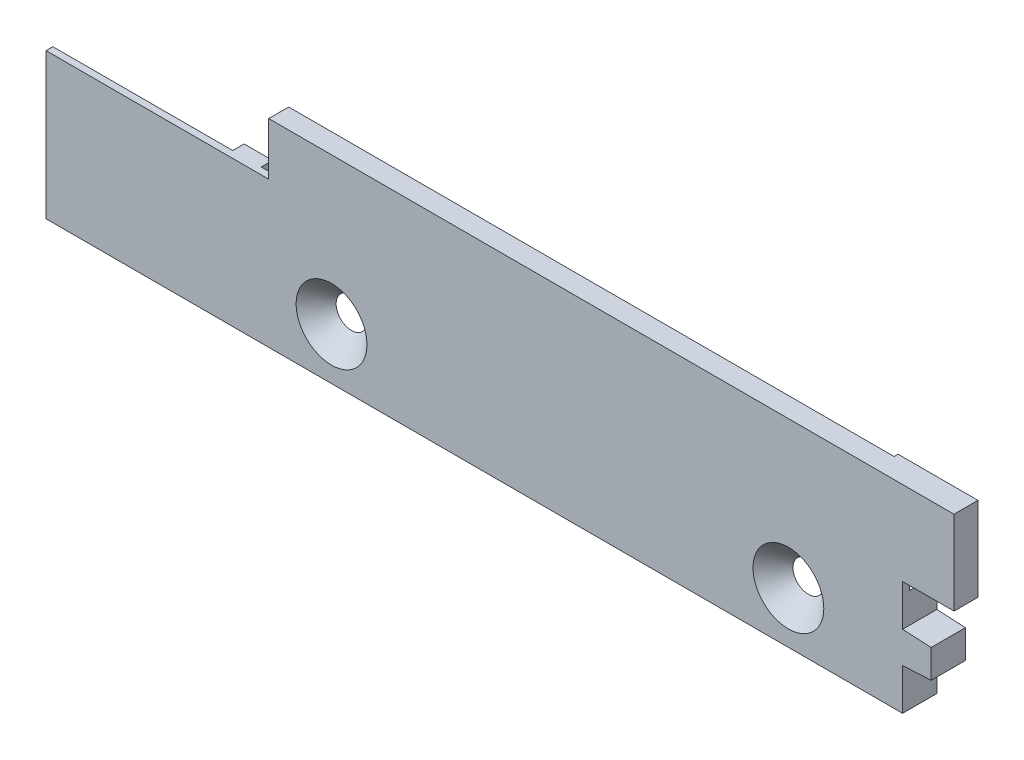
SolidWorks part; units mm, degrees
ref_plane "Front Plane" through (0, 0, 0) normal (0, 0, 1) x (1, 0, 0)
ref_plane "Top Plane" through (0, 0, 0) normal (0, 1, 0) x (1, 0, 0)
ref_plane "Right Plane" through (0, 0, 0) normal (1, 0, 0) x (0, 0, -1)
ref_axis "X-Axis" through (0, 0, 0) along (1, 0, 0)
ref_axis "Y-Axis" through (0, 42.2917, 0) along (0, -1, 0)
ref_axis "Z-Axis" through (0, 0, 55.0015) along (0, 0, -1)
sketch "Sketch1" plane through (0, 0, 0) normal (0, 0, 1) x (1, 0, 0)
  line L1 (-127.8191, -9.8629) -> (22.1809, -9.8629)
  line L2 (22.1809, -9.8629) -> (22.1809, -2.6129)
  line L3 (22.1809, -2.6129) -> (27.1809, -2.6129)
  line L4 (27.1809, -2.6129) -> (27.1809, 2.8871)
  line L5 (27.1809, 2.8871) -> (22.1809, 2.8871)
  line L6 (22.1809, 2.8871) -> (22.1809, 10.1371)
  line L7 (22.1809, 10.1371) -> (31.1809, 10.1371)
  line L8 (31.1809, 10.1371) -> (31.1809, 23.6371)
  line L10 (-127.8191, 15.6371) -> (-127.8191, -9.8629)
  line L12 (-88.8191, -25.8695) -> (-88.8191, 48.9262) construction
  line L13 (31.1809, 13.1371) -> (10.3885, 13.1371) construction
  line L14 (31.1809, 23.6371) -> (-88.8191, 23.6371) construction
  line L15 (-88.8191, 23.6371) -> (-88.8191, 15.6371)
  line L16 (-88.8191, 15.6371) -> (-127.8191, 15.6371)
  line L17 (31.1809, 23.6371) -> (31.1809, 24.8371)
  line L18 (31.1809, 24.8371) -> (-88.8191, 24.8371)
  line L19 (-88.8191, 24.8371) -> (-88.8191, 23.6371)
  point P5 (27.1809, 0.1371)
  dimension "D2" = 10
  dimension "D3" = 20
  dimension "D4" = 5.5
  dimension "D5" = 9
  dimension "D6" = 150
  dimension "D7" = 120
  dimension "D8" = 5
  dimension "D10" = 3
  dimension "D11" = 8
  dimension "D12" = 10.5
  dimension "D13" = 1.2
extrude "Boss-Extrude1" add sketch "Sketch1" along normal blind 6 and the other way blind 6
sketch "Sketch2" plane through (-127.8191, 0, 0) normal (-1, 0, 0) x (0, 0, 1)
  line L0 (-6, -9.8629) -> (6, -9.8629) construction
  line L1 (-4.8, 23.1371) -> (4.8, 23.1371) construction
  line L2 (-4.8, 23.1371) -> (-4.8, 8.1371)
  line L3 (-4.8, 8.1371) -> (4.8, 8.1371)
  line L4 (4.8, 23.1371) -> (4.8, 8.1371)
  line L5 (-6, 24.8371) -> (-6, 15.6371) construction
  line L7 (-6, 2.8871) -> (6, 2.8871) construction
  line L8 (-6, 15.6371) -> (-6, -9.8629) construction
  line L9 (6, 15.6371) -> (6, -9.8629) construction
  line L10 (0, 2.8871) -> (0, 23.1371) construction
  line L11 (-4.8, 23.1371) -> (-1.8, 23.1371)
  line L12 (-1.8, 23.1371) -> (-1.8, 24.8371)
  line L13 (-6, 24.8371) -> (6, 24.8371) construction
  line L14 (-1.8, 24.8371) -> (1.8, 24.8371)
  line L15 (1.8, 24.8371) -> (1.8, 23.1371)
  line L16 (1.8, 23.1371) -> (4.8, 23.1371)
  point P6 (0, 23.1371)
  dimension "D1" = 9.6
  dimension "D2" = 33
  dimension "D3" = 3
  dimension "D4" = 3
  dimension "D6" = 18
  dimension "D7" = 1.2
extrude "Cut-Extrude1" cut sketch "Sketch2" against normal offset from surface (157 mm away) 2 up to face at (31.1809, 17.4871, 0)
sketch "Sketch8" plane through (0, 0, 0) normal (0, 0, 1) x (1, 0, 0)
  line L0 (-127.8191, 15.6371) -> (-127.8191, -9.8629) construction
  line L1 (-107.8191, 24.8371) -> (17.1809, 24.8371)
  line L2 (-107.8191, 24.8371) -> (-107.8191, -9.8629)
  line L3 (-107.8191, -9.8629) -> (17.1809, -9.8629)
  line L4 (17.1809, 24.8371) -> (17.1809, -9.8629)
  line L5 (-127.8191, -9.8629) -> (22.1809, -9.8629) construction
  line L7 (22.1809, 2.8871) -> (22.1809, 10.1371) construction
  line L8 (29.1809, 24.8371) -> (-88.8191, 24.8371) construction
  point P12 (22.1809, 6.5121)
  dimension "D1" = 20
  dimension "D2" = 5
extrude "Cut-Extrude4" cut sketch "Sketch8" against normal blind 2.5 and the other way blind 2.5 contours L2 L3 L4 L1
sketch "Sketch9" plane through (0, 0, 0) normal (0, 0, 1) x (1, 0, 0)
  line L0 (-107.8191, -0.8629) -> (17.1809, -0.8629) construction
  line L1 (-107.8191, 8.1371) -> (-107.8191, -9.8629) construction
  line L2 (17.1809, 8.1371) -> (17.1809, -9.8629) construction
  circle A0 centre (-77.8191, -0.8629) radius 2.7
  circle A1 centre (2.1809, -0.8629) radius 2.7
  dimension "D1" = 5.4
  dimension "D2" = 80
  dimension "D3" = 15
extrude "Cut-Extrude5" cut sketch "Sketch9" against normal through all and the other way through all
chamfer "Chamfer2" distance 5 angle 3 2 edges at (27.1809, -2.6129, 0) (27.1809, 2.8871, 0) first distance on face at (24.6809, -2.6129, 0) first distance on face at (24.6809, 2.8871, 0)
sketch "Sketch14" plane through (0, 8.1371, 0) normal (0, 1, 0) x (1, 0, 0)
  line L0 (-120.3191, 4.5) -> (-115.3191, 4.5)
  line L1 (-115.3191, -4.5) -> (-120.3191, -4.5)
  line L2 (-107.8191, 0) -> (-127.8191, 0) construction
  line L3 (-107.8191, 2.5) -> (-107.8191, -2.5) construction
  line L5 (-127.8191, 4.8) -> (-127.8191, -4.8) construction
  arc A0 (-115.3191, 4.5) -> (-115.3191, -4.5) centre (-115.3191, 0) cw
  arc A1 (-120.3191, -4.5) -> (-120.3191, 4.5) centre (-120.3191, 0) cw
  point P16 (-117.8191, 0)
  dimension "D1" = 4.5
  dimension "D2" = 5
  dimension "D3" = 2.5
extrude "Cut-Extrude8" cut sketch "Sketch14" against normal blind 10
sketch "Sketch15" plane through (0, -1.8629, 0) normal (0, 1, 0) x (1, 0, 0)
  line L7 (-120.3191, -2.6) -> (-115.3191, -2.6)
  line L8 (-115.3191, 2.6) -> (-120.3191, 2.6)
  arc A2 (-120.3191, 4.5) -> (-120.3191, -4.5) centre (-120.3191, 0) ccw construction
  arc A3 (-115.3191, -4.5) -> (-115.3191, 4.5) centre (-115.3191, 0) ccw construction
  arc A6 (-120.3191, 2.6) -> (-120.3191, -2.6) centre (-120.3191, 0) ccw
  arc A7 (-115.3191, -2.6) -> (-115.3191, 2.6) centre (-115.3191, 0) ccw
  dimension "D2" = 2.6
extrude "Cut-Extrude9" cut sketch "Sketch15" against normal through all
sketch "Sketch16" plane through (0, 0, 0) normal (0, 0, 1) x (1, 0, 0)
  line L1 (-137.4451, 59.0989) -> (76.8996, 59.0989)
  line L2 (-137.4451, 59.0989) -> (-137.4451, -25.5467)
  line L3 (-137.4451, -25.5467) -> (76.8996, -25.5467)
  line L4 (76.8996, 59.0989) -> (76.8996, -25.5467)
extrude "Cut-Extrude10" cut sketch "Sketch16" against normal through all
sketch "Sketch17" plane through (0, 0, 0) normal (0, 0, -1) x (-1, 0, 0)
  line L1 (-31.1809, 24.8371) -> (-29.1809, 24.8371)
  line L2 (-31.1809, 24.8371) -> (-31.1809, 10.1371)
  line L3 (-31.1809, 10.1371) -> (-29.1809, 10.1371)
  line L4 (-29.1809, 24.8371) -> (-29.1809, 10.1371)
extrude "Cut-Extrude11" cut sketch "Sketch17" against normal up to surface (1.8 mm away) up to face at (23.1809, 23.9871, 1.8)
sketch "Sketch18" plane through (0, 0, 0) normal (0, 0, -1) x (-1, 0, 0)
  line L0 (-27.1809, 0.1371) -> (-17.1809, 0.1371) construction
  line L1 (-27.1809, 2.6251) -> (-27.1809, -2.3509) construction
  line L2 (-17.1809, 8.1371) -> (-17.1809, -9.8629) construction
  line L3 (110.3191, -5.8629) -> (125.3191, -5.8629) construction
  line L5 (117.8191, -9.8629) -> (117.8191, -1.8629) construction
  line L9 (120.3191, -1.8629) -> (115.3191, -1.8629) construction
  line L10 (120.3191, -9.8629) -> (115.3191, -9.8629) construction
  circle A0 centre (110.3191, -5.8629) radius 1.35
  circle A1 centre (125.3191, -5.8629) radius 1.35
  circle A2 centre (-22.1809, 0.1371) radius 1.35
  point P17 (117.8191, -5.8629)
  dimension "D2" = 2.7
  dimension "D1" = 15
extrude "Cut-Extrude12" cut sketch "Sketch18" against normal blind 3
chamfer "Chamfer7" distance 3.5 angle 45 2 edges at (4.8809, -0.8629, 6) (-75.1191, -0.8629, 6)
sketch "Sketch19" plane through (0, 0, 4.8) normal (0, 0, -1) x (-1, 0, 0)
  line L0 (-22.1809, 8.1371) -> (127.8191, 8.1371) construction
  line L1 (91.3191, 15.6371) -> (96.3191, 15.6371)
  line L2 (91.3191, 15.6371) -> (91.3191, 8.1371)
  line L3 (91.3191, 8.1371) -> (96.3191, 8.1371)
  line L4 (96.3191, 15.6371) -> (96.3191, 8.1371)
  line L5 (-29.1809, 10.1371) -> (-29.1809, 23.1371) construction
  dimension "D1" = 120.5
  dimension "D2" = 5
extrude "Boss-Extrude2" add sketch "Sketch19" along normal blind 2
equation "\"Largeur Bande\"= 8.3"
equation "\"Largeur Feeder\"= \"Largeur Rail\" + 1.2 + 1.2 + 0.3"
equation "\"Largeur Rail\"= \"Largeur Bande\" + 1"
equation "\"D1@Boss-Extrude1\"=\"Largeur Feeder\"/2"
equation "\"D2@Boss-Extrude1\"=\"Largeur Feeder\"/2"
